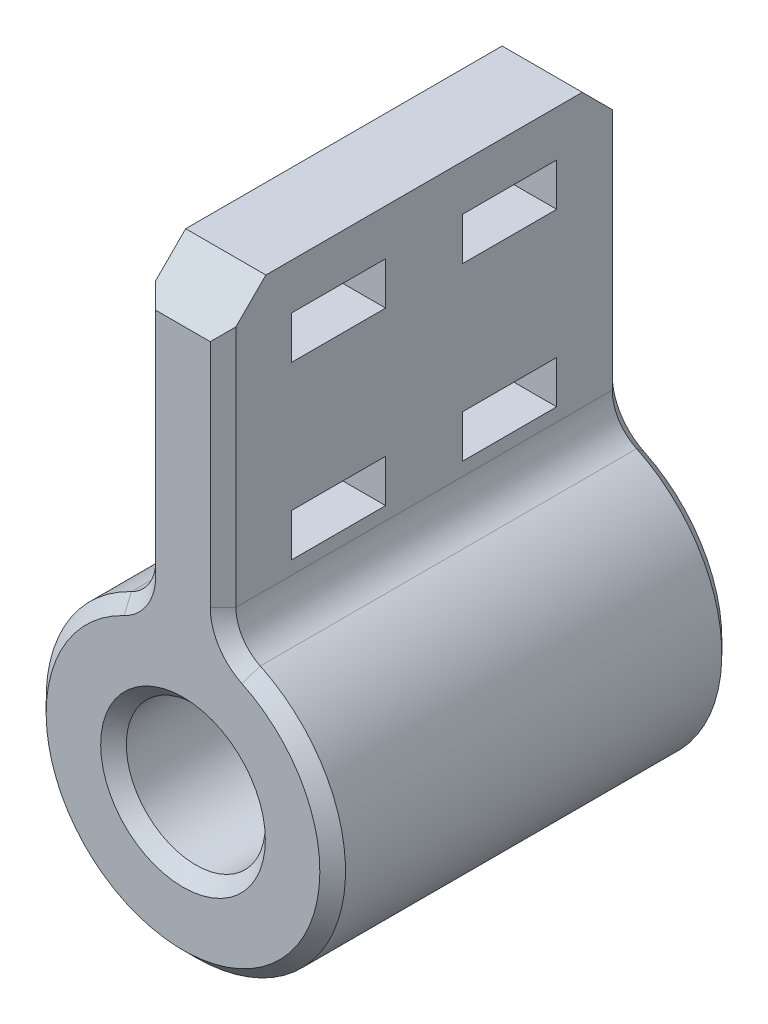
SolidWorks part; units mm, degrees
ref_plane "Front Plane" through (0, 0, 0) normal (0, 0, 1) x (1, 0, 0)
ref_plane "Top Plane" through (0, 0, 0) normal (0, 1, 0) x (1, 0, 0)
ref_plane "Right Plane" through (0, 0, 0) normal (1, 0, 0) x (0, 0, -1)
sketch "Sketch2" plane through (0, 0, 0) normal (0, 0, 1) x (1, 0, 0)
  circle A0 centre (0, 0) radius 3.5
  circle A1 centre (0, 0) radius 1.625
  dimension "D1" = 3.25
  dimension "D2" = 7
extrude "Boss-Extrude1" add sketch "Sketch2" along normal blind 9.4
sketch "Sketch3" plane through (0, 0, 9.4) normal (0, 0, 1) x (1, 0, 0)
  line L1 (-0.9375, 0) -> (0.9375, 0)
  line L2 (-0.9375, 0) -> (-0.9375, 10.4419)
  line L3 (-0.9375, 10.4419) -> (0.9375, 10.4419)
  line L4 (0.9375, 0) -> (0.9375, 10.4419)
  circle A1 centre (0, 0) radius 3.5
  circle A2 centre (0, 0) radius 3.5
  circle M3 centre (0, 0) radius 3.5
  dimension "D1" = 0.9375
  dimension "D2" = 0.9375
  dimension "D3" = 10.4419
  dimension "D4" = 0
extrude "Boss-Extrude2" add sketch "Sketch3" against normal up to surface (9.4 mm away) contours L4 L3 L2 M3 region at (0, 6.9497, 9.4) up to face at (3.5, 0, 0)
sketch "Sketch4" plane through (-0.9375, 0, 0) normal (-1, 0, 0) x (0, 0, 1)
  line L0 (9.4, 3.3721) -> (9.4, 10.4419) construction
  line L1 (1.6, 9.3721) -> (3.8, 9.3721)
  line L2 (1.6, 9.3721) -> (1.6, 8.3721)
  line L3 (1.6, 8.3721) -> (3.8, 8.3721)
  line L4 (3.8, 9.3721) -> (3.8, 8.3721)
  line L5 (5.6, 9.3721) -> (7.8, 9.3721)
  line L6 (5.6, 9.3721) -> (5.6, 8.3721)
  line L7 (5.6, 8.3721) -> (7.8, 8.3721)
  line L8 (7.8, 9.3721) -> (7.8, 8.3721)
  line L9 (1.6, 5.3721) -> (3.8, 5.3721)
  line L10 (1.6, 5.3721) -> (1.6, 4.3721)
  line L11 (1.6, 4.3721) -> (3.8, 4.3721)
  line L12 (3.8, 5.3721) -> (3.8, 4.3721)
  line L13 (5.6, 5.3721) -> (7.8, 5.3721)
  line L14 (5.6, 5.3721) -> (5.6, 4.3721)
  line L15 (5.6, 4.3721) -> (7.8, 4.3721)
  line L16 (7.8, 5.3721) -> (7.8, 4.3721)
  line L17 (0, 10.4419) -> (0, 3.3721) construction
  dimension "D1" = 1
  dimension "D2" = 2.2
  dimension "D3" = 1
  dimension "D4" = 3
  dimension "D5" = 1.6
  dimension "D6" = 1.6
extrude "Cut-Extrude2" cut sketch "Sketch4" against normal blind 10
chamfer "Chamfer2" distance 1 angle 45 2 edges at (0, 10.4419, 9.4) (0, 10.4419, 0)
fillet "Fillet1" radius 1 2 edges at (0.9375, 3.3721, 4.7) (-0.9375, 3.3721, 4.7)
chamfer "Chamfer1" distance 0.3 angle 45 12 edges at (0, -3.5, 0) (0, -3.5, 9.4) (1.625, 0, 0) (1.625, 0, 9.4) (-0.9375, 6.7517, 9.4) (0.9375, 6.7517, 9.4) (-1.0918, 3.5279, 9.4) (1.0918, 3.5279, 9.4) (-0.9375, 6.7517, 0) (0.9375, 6.7517, 0) (-1.0918, 3.5279, 0) (1.0918, 3.5279, 0)
